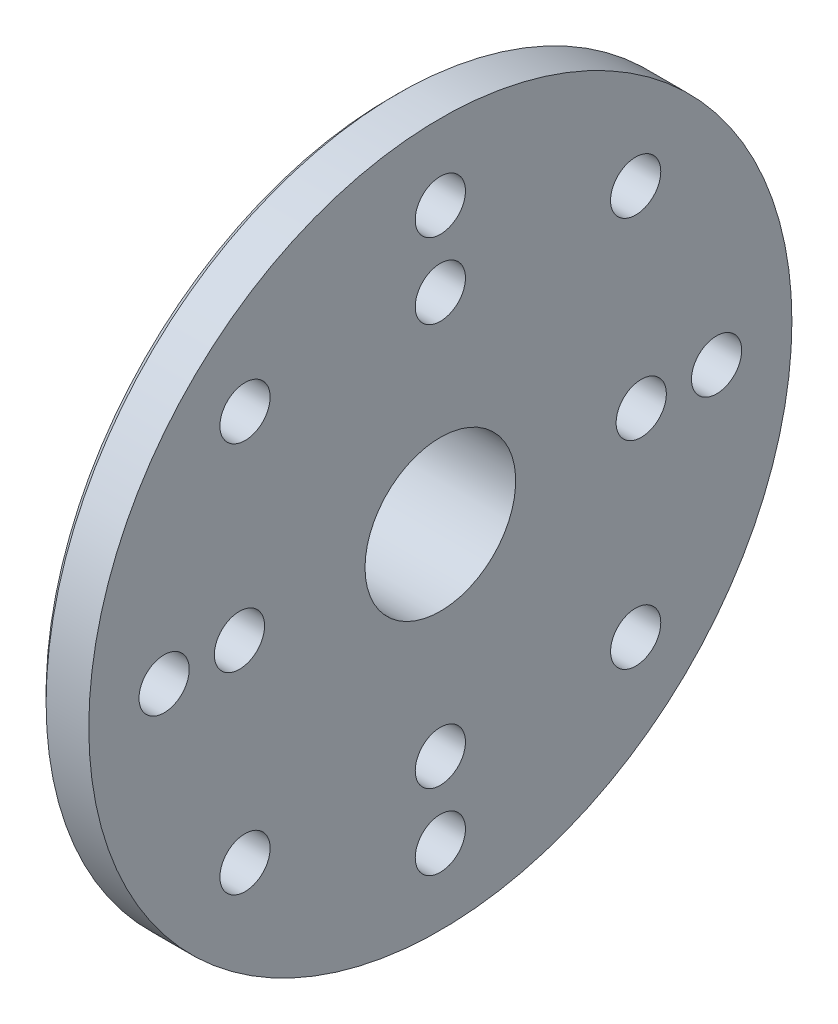
SolidWorks part; units mm, degrees
ref_plane "Ön Düzlem" through (0, 0, 0) normal (0, 0, 1) x (1, 0, 0)
ref_plane "Üst Düzlem" through (0, 0, 0) normal (0, 1, 0) x (1, 0, 0)
ref_plane "Sağ Düzlem" through (0, 0, 0) normal (1, 0, 0) x (0, 0, -1)
sketch "Sketch1" plane through (0, 0, 0) normal (0, 0, 1) x (1, 0, 0)
  line L0 (-5, 3.75) -> (-2, 3.75)
  line L1 (-2, 3.75) -> (-2, 14)
  line L2 (-2, 14) -> (0, 14)
  line L3 (0, 14) -> (0, 3)
  line L4 (0, 3) -> (-4.5, 3)
  line L5 (-4.5, 3) -> (-4.5, 1.5)
  line L6 (-4.5, 1.5) -> (-5, 1.5)
  line L7 (-5, 1.5) -> (-5, 3.75)
  line L8 (0, 0) -> (3.3862, 0) construction
  dimension "D1" = 14
  dimension "D2" = 2
  dimension "D3" = 5
  dimension "D4" = 3.75
  dimension "D5" = 1.5
  dimension "D6" = 0.5
  dimension "D7" = 3
revolve "Revolve1" add sketch "Sketch1" angle 360 about L8
sketch "Sketch2" plane through (0, 0, 0) normal (1, 0, 0) x (0, 0, -1)
  circle A0 centre (0, 0) radius 11 construction
  circle A3 centre (0, 11) radius 1
  dimension "D2" = 22
  dimension "D3" = 2
extrude "Cut-Extrude1" cut sketch "Sketch2" against normal through all
pattern_circular "CirPattern2" count 8 over 360 about axis through (0, 0, 0) along (-1, 0, 0) of "Cut-Extrude1"
sketch "Sketch3" plane through (0, 0, 0) normal (1, 0, 0) x (0, 0, -1)
  circle A0 centre (0, 0) radius 8 construction
  circle A1 centre (0, 8) radius 1
  circle A2 centre (0, 11) radius 1 construction
  dimension "D1" = 16
extrude "Cut-Extrude2" cut sketch "Sketch3" against normal through all
pattern_circular "CirPattern3" count 4 over 360 about axis through (0, 0, 0) along (-1, 0, 0) of "Cut-Extrude2"
chamfer "Chamfer1" distance 0.3 angle 45 15 edges at (-2, 0, 14) (-2, 0, 3.75) (-2, 11, -1) (-2, 7.7782, -8.7782) (-2, 0, -12) (-2, -7.7782, -8.7782) (-2, -11, -1) (-2, -7.7782, 6.7782) (-2, 0, 10) (-2, 7.7782, 6.7782) (-2, 8, -1) (-2, 0, -9) (-2, -8, -1) (-2, 0, 7) (-5, 0, 3.75)
ref_axis "Axis1" through (0, 0, 0) along (-1, 0, 0)
